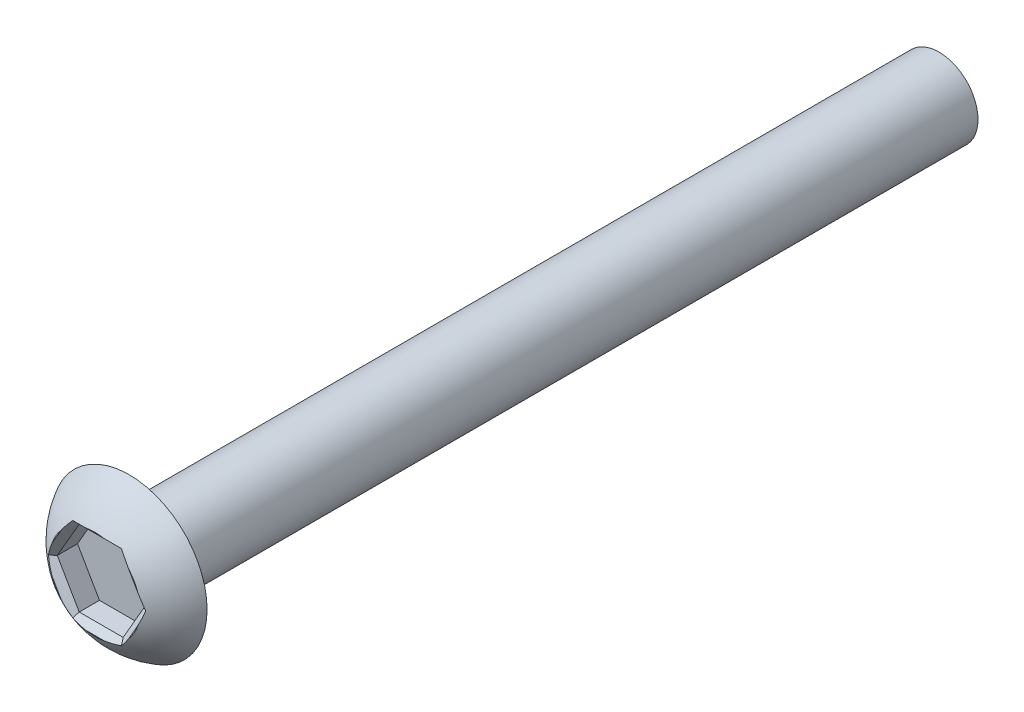
SolidWorks part; units mm, degrees
ref_plane "Front Plane" through (0, 0, 0) normal (0, 0, 1) x (1, 0, 0)
ref_plane "Top Plane" through (0, 0, 0) normal (0, 1, 0) x (1, 0, 0)
ref_plane "Right Plane" through (0, 0, 0) normal (1, 0, 0) x (0, 0, -1)
sketch "Sketch1" plane through (0, 0, 0) normal (0, 0, 1) x (1, 0, 0)
  circle A0 centre (0, 0) radius 1.25
extrude "Boss-Extrude1" add sketch "Sketch1" against normal blind 26
sketch "Sketch3" plane through (0, 0, 0) normal (1, 0, 0) x (0, 0, -1)
  line L0 (-1.5, 0) -> (-1.5, -2.0721)
  line L1 (0, 0) -> (0, 2.5)
  line L2 (-1.5, 0) -> (0, 0)
  arc A0 (-1.5, 0) -> (0, 2.5) centre (1.3333, 0) cw
  dimension "D1" = 1.5
  dimension "D2" = 2.5
revolve "Revolve1" add sketch "Sketch3" angle 360 about L2 region at (0, 0.9825, 0.6161)
sketch3d "3DSketch1" plane through (0, 0, 0) normal (0, 0, 1) x (1, 0, 0)
  dimension "D1" = 1.5
sketch "Sketch5" plane through (0, 0, 1.5) normal (0, 0, -1) x (-1, 0, 0)
  line L1 (-1.4099, 0) -> (-0.705, -1.221)
  line L2 (-0.705, -1.221) -> (0.705, -1.221)
  line L3 (0.705, -1.221) -> (1.4099, 0)
  line L4 (1.4099, 0) -> (0.705, 1.221)
  line L5 (0.705, 1.221) -> (-0.705, 1.221)
  line L6 (-0.705, 1.221) -> (-1.4099, 0)
  circle A0 centre (0, 0) radius 1.221 construction
extrude "Cut-Extrude1" cut sketch "Sketch5" along normal blind 1.25
sketch "Sketch6" plane through (0, 0, 0) normal (1, 0, 0) x (0, 0, -1)
  line L1 (-1.1, 2.3975) -> (-2.3497, 2.3975)
  line L2 (-1.1, 2.3975) -> (-1.1, -1.9866)
  line L3 (-1.1, -1.9866) -> (-2.3497, -1.9866)
  line L4 (-2.3497, 2.3975) -> (-2.3497, -1.9866)
  dimension "D1" = 1.1
extrude "Cut-Extrude2" cut sketch "Sketch6" against normal through all both and the other way through all
chamfer "Chamfer2" distance 0.2 angle 45 6 edges at (1.0574, 0.6105, 1.1) (1.0574, -0.6105, 1.1) (0, -1.221, 1.1) (-1.0574, -0.6105, 1.1) (0, 1.221, 1.1) (-1.0574, 0.6105, 1.1)
